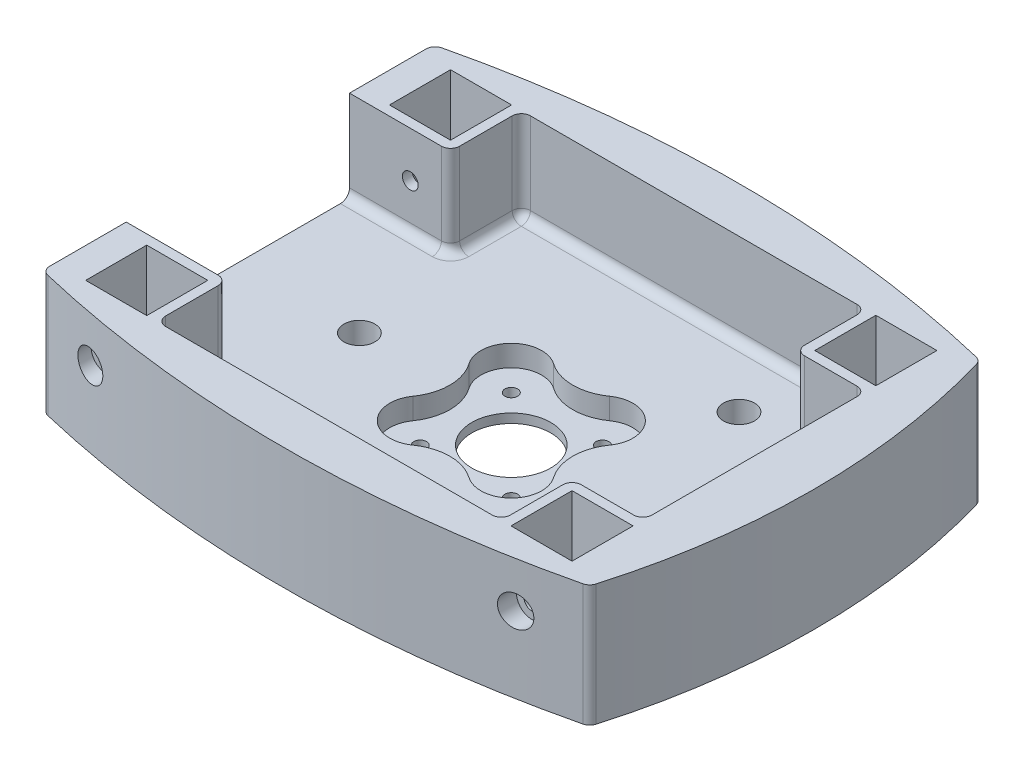
SolidWorks part; units mm, degrees
ref_plane "Front Plane" through (0, 0, 0) normal (0, 0, 1) x (1, 0, 0)
ref_plane "Top Plane" through (0, 0, 0) normal (0, 1, 0) x (1, 0, 0)
ref_plane "Right Plane" through (0, 0, 0) normal (1, 0, 0) x (0, 0, -1)
sketch "Sketch1" plane through (0, 0, 0) normal (0, 1, 0) x (1, 0, 0)
  line L0 (-140, 0) -> (0, 0) construction
  line L1 (-150.05, 10.05) -> (-129.95, 10.05)
  line L2 (-150.05, 10.05) -> (-150.05, -10.05)
  line L3 (-150.05, -10.05) -> (-129.95, -10.05)
  line L4 (-129.95, 10.05) -> (-129.95, -10.05)
  line L5 (-150.05, 10.05) -> (-129.95, -10.05) construction
  line L6 (-150.05, -10.05) -> (-129.95, 10.05) construction
  line L7 (-10.05, 10.05) -> (10.05, 10.05)
  line L8 (-10.05, 10.05) -> (-10.05, -10.05)
  line L9 (-10.05, -10.05) -> (10.05, -10.05)
  line L10 (10.05, 10.05) -> (10.05, -10.05)
  line L11 (-10.05, 10.05) -> (10.05, -10.05) construction
  line L12 (-10.05, -10.05) -> (10.05, 10.05) construction
  line L17 (-160, 14.2857) -> (-70, -50) construction
  line L18 (-150.05, -110.05) -> (-129.95, -110.05)
  line L23 (-150.05, -110.05) -> (-150.05, -89.95)
  line L24 (-150.05, -89.95) -> (-129.95, -89.95)
  line L25 (-129.95, -110.05) -> (-129.95, -89.95)
  line L26 (-150.05, -110.05) -> (-129.95, -89.95) construction
  line L27 (-150.05, -89.95) -> (-129.95, -110.05) construction
  line L28 (-10.05, -110.05) -> (10.05, -110.05)
  line L29 (-10.05, -110.05) -> (-10.05, -89.95)
  line L30 (-10.05, -89.95) -> (10.05, -89.95)
  line L31 (10.05, -110.05) -> (10.05, -89.95)
  line L32 (-10.05, -110.05) -> (10.05, -89.95) construction
  line L33 (-10.05, -89.95) -> (10.05, -110.05) construction
  line L35 (-70, -50) -> (20, -114.2857) construction
  line L37 (20, 14.2857) -> (-70, -50) construction
  line L38 (-70, -50) -> (-160, -114.2857) construction
  line L39 (-126.75, 10.05) -> (-126.75, -13.25)
  line L40 (-126.75, -13.25) -> (-150.05, -13.25)
  line L41 (-13.25, 10.05) -> (-13.25, -13.25)
  line L42 (-150.05, -86.75) -> (-126.75, -86.75)
  line L43 (-126.75, -86.75) -> (-126.75, -110.05)
  line L44 (-13.25, -13.25) -> (10.05, -13.25)
  line L45 (-13.25, -110.05) -> (-13.25, -86.75)
  line L46 (-13.25, -86.75) -> (10.05, -86.75)
  line L47 (10.05, -13.25) -> (10.05, -86.75)
  line L48 (-126.75, -110.05) -> (-13.25, -110.05)
  line L49 (-126.75, 10.05) -> (-13.25, 10.05)
  line L50 (-150.05, -13.25) -> (-150.05, -86.75)
  line L51 (-160, 14.2857) -> (-160, -114.2857)
  line L52 (-85, -35) -> (-70, -50) construction
  line L53 (-70, -50) -> (-55, -65) construction
  line L54 (-55, -35) -> (-70, -50) construction
  line L55 (-70, -50) -> (-85, -65) construction
  circle A0 centre (-70, -50) radius 8
  circle A2 centre (-120, -50) radius 5.1
  arc A5 (-160, 14.2857) -> (20, 14.2857) centre (-70, -354.9026) cw
  arc A6 (-160, -114.2857) -> (20, -114.2857) centre (-70, 254.9026) ccw
  arc A8 (20, 14.2857) -> (20, -114.2857) centre (-195.6208, -50) cw
  circle A9 centre (-70, -50) radius 11
  circle A10 centre (-35, -10.05) radius 5.1
  circle A11 centre (-35, -89.95) radius 5.1
  circle A16 centre (-85, -35) radius 2.1
  circle A17 centre (-55, -35) radius 2.1
  circle A18 centre (-55, -65) radius 2.1
  circle A19 centre (-85, -65) radius 2.1
  arc A20 (-93.168, -40.7692) -> (-79.2308, -26.832) centre (-85, -35) cw
  arc A21 (-60.7692, -26.832) -> (-46.832, -40.7692) centre (-55, -35) cw
  arc A22 (-46.832, -59.2308) -> (-60.7692, -73.168) centre (-55, -65) cw
  arc A23 (-79.2308, -73.168) -> (-93.168, -59.2308) centre (-85, -65) cw
  arc A24 (-93.168, -40.7692) -> (-93.168, -59.2308) centre (-106.2368, -50) cw
  arc A25 (-79.2308, -26.832) -> (-60.7692, -26.832) centre (-70, -13.7632) ccw
  arc A26 (-46.832, -40.7692) -> (-46.832, -59.2308) centre (-33.7632, -50) ccw
  arc A27 (-60.7692, -73.168) -> (-79.2308, -73.168) centre (-70, -86.2368) ccw
  circle A28 centre (-70, -50) radius 13
  point P0 (-140, 0)
  point P5 (0, 0)
  point P10 (0, -100)
  point P16 (-140, -100)
  dimension "D4" = 22
  dimension "D5" = 16
  dimension "D7" = 225
  dimension "D8" = 380
  dimension "D9" = 10.2
  dimension "D16" = 4.2
  dimension "D19" = 10
  dimension "D20" = 16
  dimension "D21" = 26
  dimension "D1" = 20.1
  dimension "D2" = 140
  dimension "D3" = 100
  dimension "D6" = 180
  dimension "D10" = 35
  dimension "D11" = 3.2
  dimension "D12" = 3.2
  dimension "D13" = 3.2
  dimension "D14" = 3.2
  dimension "D15" = 20
  dimension "D18" = 30
extrude "Boss-Extrude1" add sketch "Sketch1" along normal blind 40 contours A8 A5 L51 A6 A9 A10 A11 A2 L31 L28 L29 L30 L25 L18 L23 L24 L1 L4 L3 L2 L7 L10 L9 L8 region at (-70, 0, -22.6803)
extrude "Boss-Extrude2" add sketch "Sketch1<3>" along normal blind 10 contours L40 L50 L42 L43 L48 L45 L46 L47 L44 L41 L49 L39 A11 A10 A9 A2 region at (-70, 0, -8.0486)
sketch "Sketch1<3>" plane through (0, 0, 0) normal (0, 1, 0) x (1, 0, 0) same geometry as "Sketch1"
extrude "Boss-Extrude3" add sketch "Sketch1<4>" along normal blind 3 contours A27 A22 A26 A21 A25 A20 A24 A23 A28 A19 A18 A17 A16 region at (-91.5711, 0, 28.4289)
sketch "Sketch1<4>" plane through (0, 0, 0) normal (0, 1, 0) x (1, 0, 0) same geometry as "Sketch1"
sketch "Sketch2" plane through (0, 0, 13.25) normal (0, 0, 1) x (1, 0, 0)
  line L0 (-150.05, 40) -> (-129.95, 40) construction
  line L1 (-126.75, 40) -> (-150.05, 40) construction
  line L2 (-129.95, 40) -> (-129.95, 10) construction
  line L3 (-150.05, 40) -> (-129.95, 10) construction
  line L4 (-129.95, 40) -> (-129.95, 0) construction
  line L5 (-129.95, 10) -> (-150.05, 10) construction
  line L6 (-150.05, 40) -> (-150.05, 0) construction
  line L7 (-150.05, 10) -> (-150.05, 40) construction
  line L8 (-10.05, 40) -> (10.05, 40) construction
  line L9 (10.05, 40) -> (10.05, 10) construction
  line L10 (10.05, 10) -> (-10.05, 10) construction
  line L11 (-10.05, 10) -> (-10.05, 40) construction
  line L12 (-129.95, 40) -> (-150.05, 10) construction
  line L13 (10.05, 40) -> (-10.05, 10) construction
  line L14 (-10.05, 40) -> (10.05, 10) construction
  circle A0 centre (-140, 25) radius 2.6
  circle A2 centre (0, 25) radius 2.6
  circle A5 centre (0, 25) radius 5.05
  circle A6 centre (-140, 25) radius 5.05
  dimension "D1" = 5.2
  dimension "D2" = 10.1
extrude "Cut-Extrude1" cut sketch "Sketch2" against normal blind 62 contours A6 A0 | A0 | A5 A2 | A2 region at (-140, 25, 13.25) region at (0, 25, 13.25) region at (-4.9072, 25, 13.25) region at (-144.9072, 25, 13.25)
extrude "Boss-Extrude5" add sketch "Sketch2<3>" against normal blind 26.5
sketch "Sketch2<3>" plane through (0, 0, 13.25) normal (0, 0, 1) x (1, 0, 0) same geometry as "Sketch2"
extrude "Cut-Extrude2" cut sketch "Sketch2<4>" against normal up to surface (23.3 mm away) up to face at (-145.05, 25, -10.05)
sketch "Sketch2<4>" plane through (0, 0, 13.25) normal (0, 0, 1) x (1, 0, 0) same geometry as "Sketch2"
extrude "Boss-Extrude6" add sketch "Sketch2<5>" against normal up to surface (3.2 mm away) up to face at (-145.05, 25, 10.05)
sketch "Sketch2<5>" plane through (0, 0, 13.25) normal (0, 0, 1) x (1, 0, 0) same geometry as "Sketch2"
extrude "Cut-Extrude3" cut sketch "Sketch2<6>" along normal blind 127.2 contours A6 A0 | A5 A2 | A2 | A0 region at (-140, 25, 13.25) region at (0, 25, 13.25) region at (-4.9072, 25, 13.25) region at (-144.9072, 25, 13.25)
sketch "Sketch2<6>" plane through (0, 0, 13.25) normal (0, 0, 1) x (1, 0, 0) same geometry as "Sketch2"
extrude "Boss-Extrude7" add sketch "Sketch2<7>" along normal blind 100 contours A6 A0 | A5 A2 region at (-4.9072, 25, 13.25) region at (-144.9072, 25, 13.25)
sketch "Sketch2<7>" plane through (0, 0, 13.25) normal (0, 0, 1) x (1, 0, 0) same geometry as "Sketch2"
extrude "Cut-Extrude4" cut sketch "Sketch2<8>" along normal up to surface (96.8 mm away) up to face at (-145.05, 25, 110.05)
sketch "Sketch2<8>" plane through (0, 0, 13.25) normal (0, 0, 1) x (1, 0, 0) same geometry as "Sketch2"
extrude "Boss-Extrude8" add sketch "Sketch2<9>" along normal up to surface (76.7 mm away) up to face at (-145.05, 25, 89.95)
sketch "Sketch2<9>" plane through (0, 0, 13.25) normal (0, 0, 1) x (1, 0, 0) same geometry as "Sketch2"
extrude "Cut-Extrude5" cut sketch "Sketch2<10>" along normal up to surface (73.5 mm away) contours A6 A0 | A0 | A5 A2 | A2 region at (-140, 25, 13.25) region at (0, 25, 13.25) region at (-4.9072, 25, 13.25) region at (-144.9072, 25, 13.25) up to face at (-5.05, 25, 86.75)
sketch "Sketch2<10>" plane through (0, 0, 13.25) normal (0, 0, 1) x (1, 0, 0) same geometry as "Sketch2"
sketch "Sketch3" plane through (-150.05, 0, 0) normal (1, 0, 0) x (0, 0, -1)
  line L0 (-86.75, 40) -> (-86.75, 10)
  line L1 (-86.75, 10) -> (-13.25, 10)
  line L2 (-13.25, 10) -> (-86.75, 10) construction
  line L3 (-13.25, 40) -> (-13.25, 10) construction
  line L4 (-13.25, 10) -> (-13.25, 40)
  line L5 (-13.25, 40) -> (-86.75, 40) construction
  line L6 (-13.25, 40) -> (-86.75, 40)
extrude "Cut-Extrude6" cut sketch "Sketch3" against normal blind 10
fillet "Fillet1" radius 3 25 edges at (-13.25, 10, 98.4) (-1.6, 10, 13.25) (-143.375, 10, 86.75) (-126.75, 10, 1.6) (-160, 20, -14.2857) (20, 20, 114.2857) (20, 20, -14.2857) (-160, 20, 114.2857) (-13.25, 25, 110.05) (-1.6, 10, 86.75) (-13.25, 25, 86.75) (10.05, 25, 86.75) (10.05, 25, 13.25) (10.05, 10, 50) (-13.25, 25, 13.25) (-13.25, 10, 1.6) (-13.25, 25, -10.05) (-70, 10, 110.05) (-126.75, 10, 98.4) (-126.75, 25, 110.05) (-126.75, 25, 86.75) (-70, 10, -10.05) (-143.375, 10, 13.25) (-126.75, 25, 13.25) (-126.75, 25, -10.05)
